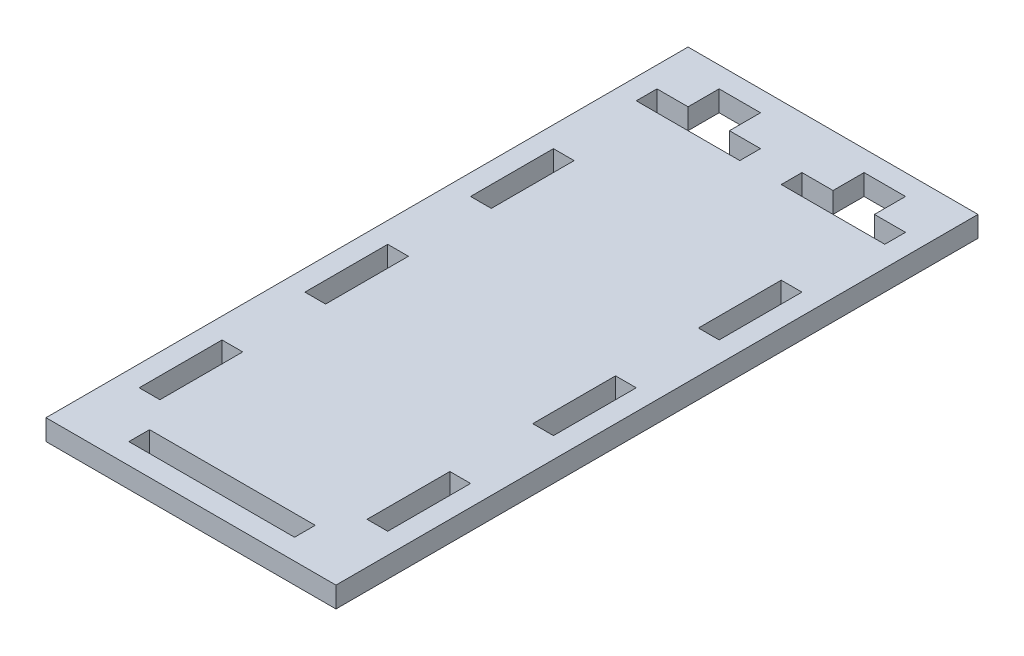
SolidWorks part; units mm, degrees
ref_plane "Plan de face" through (0, 0, 0) normal (0, 0, 1) x (1, 0, 0)
ref_plane "Plan de dessus" through (0, 0, 0) normal (0, 1, 0) x (1, 0, 0)
ref_plane "Plan de droite" through (0, 0, 0) normal (1, 0, 0) x (0, 0, -1)
sketch "Esquisse1" plane through (0, 0, 0) normal (0, 1, 0) x (1, 0, 0)
  line L0 (-22.5, 77.5) -> (-12.5, 77.5)
  line L1 (-12.5, 77.5) -> (-12.5, 70)
  line L2 (25, 45) -> (30, 45)
  line L3 (-30, 45) -> (-25, 45)
  line L4 (-30, 45) -> (-30, 25)
  line L5 (-35, 82.5) -> (35, 82.5)
  line L6 (-35, 82.5) -> (-35, -72.5)
  line L7 (-35, -72.5) -> (35, -72.5)
  line L8 (35, 82.5) -> (35, -72.5)
  line L9 (-12.5, 70) -> (-5, 70)
  line L10 (-5, 70) -> (-5, 65)
  line L11 (-5, 65) -> (-30, 65)
  line L12 (-30, 65) -> (-30, 70)
  line L13 (-30, 70) -> (-22.5, 70)
  line L14 (-22.5, 70) -> (-22.5, 77.5)
  line L15 (12.5, 77.5) -> (22.5, 77.5)
  line L16 (22.5, 77.5) -> (22.5, 70)
  line L17 (22.5, 70) -> (30, 70)
  line L18 (30, 70) -> (30, 65)
  line L19 (30, 65) -> (5, 65)
  line L20 (5, 65) -> (5, 70)
  line L21 (5, 70) -> (12.5, 70)
  line L22 (12.5, 70) -> (12.5, 77.5)
  line L23 (-30, 25) -> (-25, 25)
  line L24 (-25, 45) -> (-25, 25)
  line L25 (-30, 5) -> (-25, 5)
  line L26 (-30, 5) -> (-30, -15)
  line L27 (-30, -15) -> (-25, -15)
  line L28 (-25, 5) -> (-25, -15)
  line L29 (-30, -35) -> (-25, -35)
  line L30 (-30, -35) -> (-30, -55)
  line L31 (-30, -55) -> (-25, -55)
  line L32 (-25, -35) -> (-25, -55)
  line L33 (25, 45) -> (25, 25)
  line L34 (25, 25) -> (30, 25)
  line L35 (30, 45) -> (30, 25)
  line L36 (25, 5) -> (30, 5)
  line L37 (25, 5) -> (25, -15)
  line L38 (25, -15) -> (30, -15)
  line L39 (30, 5) -> (30, -15)
  line L40 (25, -35) -> (30, -35)
  line L41 (25, -35) -> (25, -55)
  line L42 (25, -55) -> (30, -55)
  line L43 (30, -35) -> (30, -55)
  line L45 (-20, -62.5) -> (20, -62.5)
  line L46 (-20, -62.5) -> (-20, -67.5)
  line L47 (-20, -67.5) -> (20, -67.5)
  line L48 (20, -62.5) -> (20, -67.5)
  dimension "D1" = 10
  dimension "D3" = 35
  dimension "D4" = 5
  dimension "D5" = 82.5
  dimension "D6" = 20
  dimension "D7" = 70
  dimension "D8" = 155
  dimension "D9" = 7.5
  dimension "D10" = 7.5
  dimension "D11" = 5
  dimension "D12" = 25
  dimension "D13" = 5
  dimension "D14" = 5
  dimension "D15" = 5
  dimension "D16" = 7.5
  dimension "D17" = 7.5
  dimension "D18" = 25
  dimension "D19" = 5
  dimension "D20" = 5
  dimension "D21" = 5
  dimension "D22" = 5
  dimension "D23" = 10
  dimension "D24" = 5
  dimension "D25" = 5
  dimension "D26" = 20
  dimension "D27" = 20
  dimension "D28" = 20
  dimension "D29" = 5
  dimension "D30" = 20
  dimension "D31" = 5
  dimension "D32" = 20
  dimension "D33" = 5
  dimension "D34" = 5
  dimension "D35" = 5
  dimension "D36" = 5
  dimension "D37" = 20
  dimension "D38" = 20
  dimension "D39" = 20
  dimension "D40" = 20
  dimension "D41" = 20
  dimension "D42" = 20
  dimension "D43" = 5
  dimension "D44" = 5
  dimension "D45" = 5
  dimension "D46" = 40
  dimension "D47" = 15
  dimension "D48" = 5
  dimension "D49" = 5
extrude "Boss.-Extru.1" add sketch "Esquisse1" along normal blind 5
